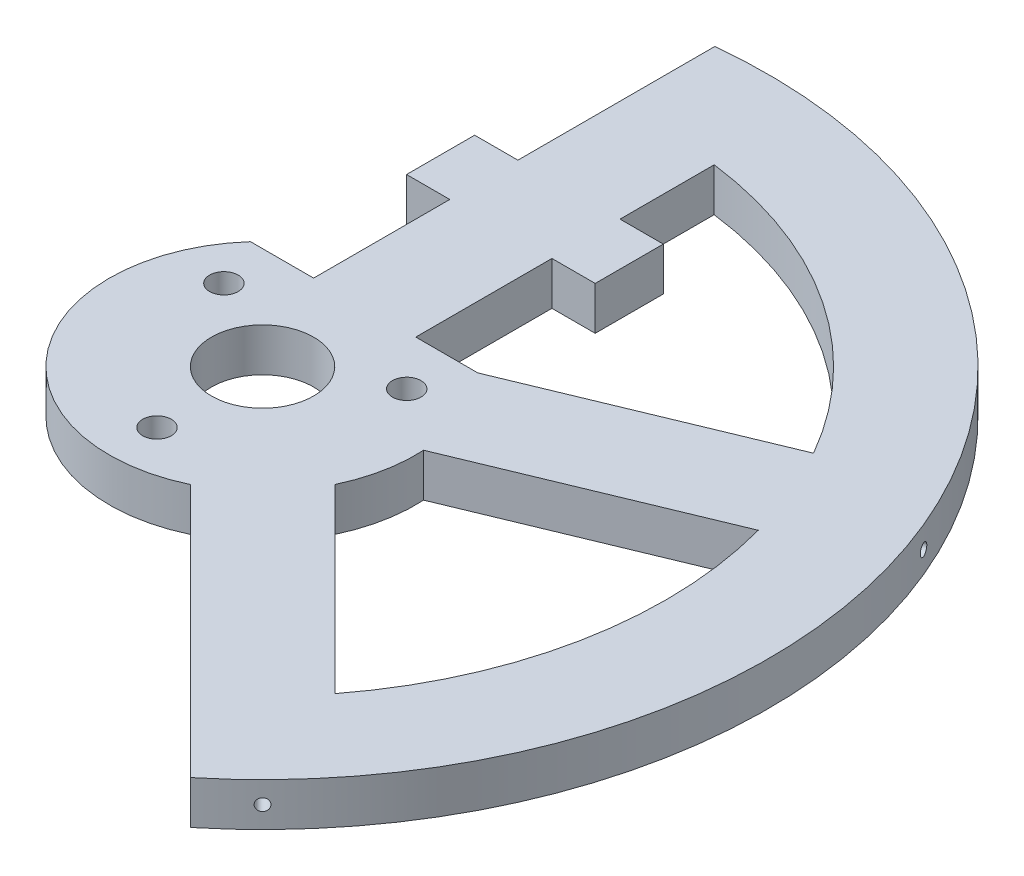
SolidWorks part; units mm, degrees
ref_plane "Front Plane" through (0, 0, 0) normal (0, 0, 1) x (1, 0, 0)
ref_plane "Top Plane" through (0, 0, 0) normal (0, 1, 0) x (1, 0, 0)
ref_plane "Right Plane" through (0, 0, 0) normal (1, 0, 0) x (0, 0, -1)
sketch "Sketch1" plane through (0, 0, 0) normal (0, 1, 0) x (1, 0, 0)
  line L0 (0, 0) -> (0, 74.3) construction
  line L1 (0, 0) -> (52.538, -52.538) construction
  line L2 (20.3033, -9.6967) -> (46.898, -36.2914)
  line L3 (7.5, 15) -> (7.5, 35)
  line L4 (-7.5, -3.1066) -> (-5.3033, -5.3033) construction
  line L5 (-7.5, 21.2132) -> (-7.5, 14.1697) construction
  line L6 (-7.5, -3.1066) -> (-7.5, 74.3) construction
  line L7 (7.5, 3.1066) -> (7.5, 74.3) construction
  line L8 (-7.5, -3.1066) -> (47.2347, -57.8413) construction
  line L9 (7.5, 3.1066) -> (57.8413, -47.2347) construction
  line L10 (46.898, -36.2914) -> (57.573, -46.9664) construction
  line L11 (7.5, 58.8238) -> (7.5, 73.9205) construction
  line L12 (0, 0) -> (68.6442, 28.4334) construction
  line L13 (22.4686, 1.1888) -> (57.2162, 15.5818)
  line L14 (-2.8701, 6.9291) -> (0, 8.1179) construction
  line L15 (2.8701, -6.9291) -> (5.7403, -5.7403) construction
  line L16 (2.8701, -6.9291) -> (71.5144, 21.5043) construction
  line L17 (5.7403, -5.7403) -> (13.2403, -2.6336) construction
  line L18 (7.5, 3.1066) -> (13.2403, -2.6336) construction
  line L19 (7.5, 3.1066) -> (7.5, 11.2245) construction
  line L20 (0, 8.1179) -> (7.5, 11.2245) construction
  line L21 (7.5, 11.2245) -> (9.0849, 11.881) construction
  line L22 (-2.8701, 6.9291) -> (65.7741, 35.3625) construction
  line L23 (51.476, 29.44) -> (65.4235, 35.2172) construction
  line L24 (65.4235, 35.2172) -> (65.7741, 35.3625)
  line L25 (57.2162, 15.5818) -> (71.1638, 21.3591) construction
  line L26 (71.1638, 21.3591) -> (71.5144, 21.5043)
  line L27 (13.2403, -2.6336) -> (20.3033, -9.6967) construction
  line L28 (13.85, 5) -> (7.5, 5) construction
  line L29 (13.85, 17.7321) -> (13.85, 15) construction
  line L30 (13.85, 45) -> (7.5, 45)
  line L31 (-13.85, 17.7321) -> (-13.85, 15) construction
  line L32 (13.85, 5) -> (-13.85, 45) construction
  line L33 (13.85, 45) -> (-13.85, 5) construction
  line L34 (-13.85, 35) -> (-7.5, 35)
  line L35 (-13.85, 35) -> (-13.85, 15) construction
  line L36 (-16.7705, 15) -> (-7.5, 15)
  line L37 (-7.5, 35) -> (-7.5, 15)
  line L38 (7.5, 15) -> (16.6148, 15)
  line L39 (7.5, 15) -> (7.5, 35)
  line L40 (7.5, 35) -> (13.85, 35)
  line L41 (13.85, 15) -> (13.85, 35) construction
  line L42 (13.2403, -2.6336) -> (22.4686, 1.1888) construction
  line L43 (7.5, 5) -> (-7.5274, 5) construction
  line L44 (-7.5, 5) -> (-13.85, 5) construction
  line L45 (-7.5274, 5) -> (0, 5) construction
  line L46 (0, 5) -> (-7.5, 5) construction
  line L47 (13.85, 5) -> (13.85, 13.8548) construction
  line L48 (16.6148, 15) -> (16.7283, 15.047)
  line L49 (16.7283, 15.047) -> (51.476, 29.44)
  line L50 (13.85, 13.8548) -> (13.85, 17.7321) construction
  line L51 (9.0849, 11.881) -> (13.85, 13.8548) construction
  line L52 (7.5, 11.2245) -> (7.5, 21.2132) construction
  line L53 (7.5, 21.2132) -> (7.5, 14.1697) construction
  line L54 (-5.3033, -5.3033) -> (9.6967, -20.3033) construction
  line L55 (9.6967, -20.3033) -> (46.9664, -57.573)
  line L56 (-7.5, -3.1066) -> (-7.5, 0) construction
  line L57 (-7.5, 0) -> (-7.5, 5) construction
  line L58 (-13.85, 5) -> (-13.85, 17.7321) construction
  line L59 (-7.5, 5) -> (-7.5, 21.2132) construction
  line L60 (-7.5, 14.1697) -> (-7.5, 15) construction
  line L61 (-7.5, 15) -> (-7.5, 35) construction
  line L62 (-13.85, 15) -> (-13.85, 35) construction
  line L63 (-13.85, 35) -> (-13.85, 45)
  line L64 (13.85, 15) -> (13.85, 35) construction
  line L65 (13.85, 35) -> (13.85, 45)
  line L66 (0, 45) -> (-7.5, 45) construction
  line L67 (-7.5, 45) -> (-13.85, 45)
  line L68 (7.5, 45) -> (0, 45) construction
  line L69 (7.5, 14.1697) -> (7.5, 15) construction
  line L70 (7.5, 35.8303) -> (7.5, 45) construction
  line L71 (7.5, 45) -> (7.5, 58.8238)
  line L72 (7.5, 35) -> (7.5, 35.8303) construction
  line L73 (-7.5, 35) -> (-7.5, 35.8303) construction
  line L74 (-7.5, 45) -> (-7.5, 73.9205)
  line L75 (-7.5, 35.8303) -> (-7.5, 45) construction
  line L77 (13.85, 13.8548) -> (16.6148, 15) construction
  arc A0 (46.9664, -57.573) -> (-7.5, 73.9205) centre (0, 0) ccw
  arc A1 (46.898, -36.2914) -> (57.2162, 15.5818) centre (0, 0) ccw
  arc A2 (-7.5, 73.9205) -> (46.9664, -57.573) centre (0, 0) ccw construction
  circle A3 centre (0, 0) radius 74.3 construction
  arc A4 (41.9314, -41.9314) -> (46.898, -36.2914) centre (0, 0) ccw construction
  circle A5 centre (0, 0) radius 59.3 construction
  arc A6 (36.2914, -46.898) -> (41.9314, -41.9314) centre (0, 0) ccw construction
  arc A7 (-7.5, 58.8238) -> (36.2914, -46.898) centre (0, 0) ccw construction
  arc A8 (7.5, 58.8238) -> (0, 59.3) centre (0, 0) ccw construction
  arc A9 (0, 59.3) -> (-7.5, 58.8238) centre (0, 0) ccw construction
  arc A10 (57.2162, 15.5818) -> (54.7861, 22.6931) centre (0, 0) ccw construction
  arc A11 (51.476, 29.44) -> (7.5, 58.8238) centre (0, 0) ccw
  arc A12 (54.7861, 22.6931) -> (51.476, 29.44) centre (0, 0) ccw construction
  arc A13 (20.3033, -9.6967) -> (22.4686, 1.1888) centre (0, 0) ccw
  circle A14 centre (0, 0) radius 7.5
  arc A15 (9.6967, -20.3033) -> (15.9099, -15.9099) centre (0, 0) ccw construction
  arc A16 (15.9099, -15.9099) -> (20.3033, -9.6967) centre (0, 0) ccw construction
  arc A17 (22.4686, 1.1888) -> (20.7873, 8.6104) centre (0, 0) ccw construction
  arc A18 (16.7283, 15.047) -> (13.85, 17.7321) centre (0, 0) ccw construction
  arc A19 (20.7873, 8.6104) -> (16.7283, 15.047) centre (0, 0) ccw construction
  arc A20 (13.85, 17.7321) -> (1.7801, 22.4295) centre (0, 0) ccw construction
  arc A21 (-7.5, 21.2132) -> (-13.85, 17.7321) centre (0, 0) ccw construction
  arc A22 (1.7801, 22.4295) -> (-13.85, 17.7321) centre (0, 0) ccw construction
  arc A23 (7.5, 21.2132) -> (0, 22.5) centre (0, 0) ccw construction
  arc A24 (0, 22.5) -> (-7.5, 21.2132) centre (0, 0) ccw construction
  arc A25 (-1.7801, 22.4295) -> (-13.85, 17.7321) centre (0, 0) ccw construction
  arc A26 (-16.7705, 15) -> (9.6967, -20.3033) centre (0, 0) ccw
  arc A27 (-13.85, 17.7321) -> (-16.7705, 15) centre (0, 0) ccw construction
  arc A28 (-16.7705, 15) -> (-1.7801, 22.4295) centre (0, 0) ccw construction
  arc A29 (-13.85, 17.7321) -> (-16.7705, 15) centre (0, 0) ccw construction
  arc A30 (-13.85, 17.7321) -> (-16.7705, 15) centre (0, 0) ccw construction
  arc A31 (-16.7705, 15) -> (7.5, 21.2132) centre (0, 0) ccw construction
  point P76 (0, 0)
  point P77 (0, 25)
  point P80 (16.6148, 15)
  point P81 (16.6148, 15)
  point P83 (16.2894, 14.8652)
  point P85 (16.5935, 15)
  point P86 (13.85, 16.295)
  point P87 (13.85, 15)
  point P88 (-13.85, 15)
  dimension "D1" = 148.6
  dimension "D11" = 45
  dimension "D12" = 15
  dimension "D2" = 135
  dimension "D6" = 67.5
  dimension "D9" = 27.7
  dimension "D10" = 40
  dimension "D13" = 5
  dimension "D14" = 10
  dimension "D15" = 10
  dimension "D3" = 7.5
  dimension "D4" = 7.5
  dimension "D5" = 15
  dimension "D7" = 7.5
  dimension "D8" = 7.5
extrude "Boss-Extrude1" add sketch "Sketch1" along normal mid plane 6.35 contours L31 A26 L55 A0 L74 L67 L63 L34 L37 L36 L49 A18 L29 L38 L3 L40 L65 L30 L71 A11 L2 A13 L13 A1 A14 region at (27.267, 0, -11.9761)
hole_wizard "M5x0.8 Tapped Hole2" positions "Sketch2" profile "Sketch3" tap size "M5x0.8" standard "ANSI Metric" end condition through all
sketch "Sketch2" plane through (0, 3.175, 0) normal (0, 1, 0) x (1, 0, 0)
  line L1 (0, 0) -> (-13.4234, 7.75) construction
  line L3 (13.4234, 7.75) -> (0, 0) construction
  line L4 (0, 0) -> (0, -15.5) construction
  circle A0 centre (0, 0) radius 15.5 construction
  point P10 (-13.4234, 7.75)
  point P12 (13.4234, 7.75)
  point P16 (0, -15.5)
  point P17 (15.5, 0)
  point P18 (13.4443, 7.7862)
  point P19 (0, 0)
  dimension "D1" = 31
  dimension "D2" = 120
  dimension "D3" = 120
sketch "Sketch3" plane through (0, 3.175, 15.5) normal (1, 0, 0) x (0, 0, 1)
  line L0 (0, 0) -> (0, 6.35)
  line L1 (0, 6.35) -> (2.1, 6.35)
  line L2 (2.1, 6.35) -> (2.1, 0)
  line L5 (2.1, 0) -> (0, 0)
  line L11 (0, -6.35) -> (0, 107.95) construction
  dimension "Thru Tap Drill Dia." = 4.2
  dimension "Thru Tap Drill Depth" = 6.35
ref_plane "Plane1" through (0, 0, -74.3) normal (0, 0, -1) x (-1, 0, 0)
hole_wizard "M2.2x0.45 Tapped Hole1" positions "Sketch4" profile "Sketch5" tap size "M2.2x0.45" standard "ANSI Metric"
sketch "Sketch4" plane through (0, 0, -74.3) normal (0, 0, -1) x (-1, 0, 0)
  point P0 (0, 0)
sketch "Sketch5" plane through (0, 0, -74.3) normal (1, 0, 0) x (0, 1, 0)
  line L0 (0, 0) -> (0, 10.5258)
  line L1 (0, 10.5258) -> (0.875, 10)
  line L2 (0.875, 10) -> (0.875, 0)
  line L5 (0.875, 0) -> (0, 0)
  line L10 (0, 10.5258) -> (-0.875, 10) construction
  line L11 (0, -6.35) -> (0, 107.95) construction
  dimension "Tap Drill Dia." = 1.75
  dimension "Tap Drill Depth" = 10
  dimension "Drill Angle" = 118
pattern_circular "CirPattern1" count 3 over 135 about axis through (0, 3.175, 0) along (0, -1, 0) of "M2.2x0.45 Tapped Hole1"
